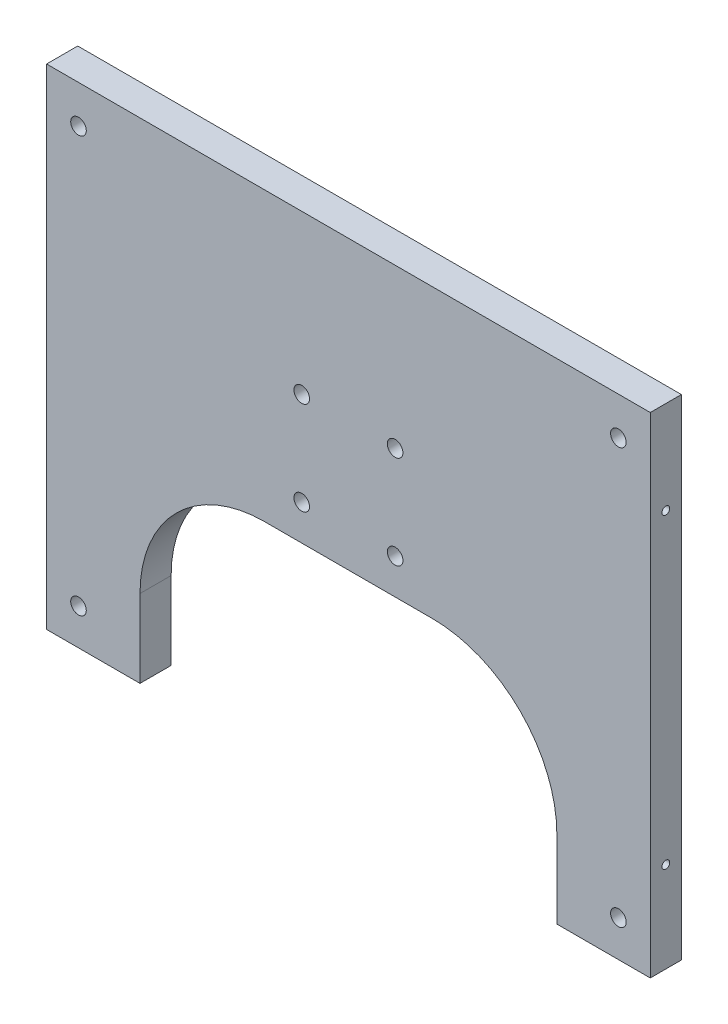
SolidWorks part; units mm, degrees
material "Beech"
ref_plane "Front Plane" through (0, 0, 0) normal (0, 0, 1) x (1, 0, 0)
ref_plane "Top Plane" through (0, 0, 0) normal (0, 1, 0) x (1, 0, 0)
ref_plane "Right Plane" through (0, 0, 0) normal (1, 0, 0) x (0, 0, -1)
sketch "Sketch1" plane through (0, 0, 0) normal (0, 0, 1) x (1, 0, 0)
  line L0 (258.9335, 10.7139) -> (12.7, 10.7139)
  line L1 (135.8167, -73.0143) -> (135.8167, 40.1583) construction
  line L2 (12.7, 10.7139) -> (12.7, -189.0518)
  line L3 (12.7, -189.0518) -> (50.8, -189.0518)
  line L4 (50.8, -189.0518) -> (50.8, -106.5018)
  line L5 (50.8, -106.5018) -> (220.8335, -106.5018)
  line L6 (135.8167, -205.9834) -> (135.8167, -73.0143) construction
  line L7 (135.8167, -106.5018) -> (135.8167, 10.7139) construction
  line L8 (271.3655, 10.7139) -> (0, 10.7139) construction
  line L9 (12.7, -189.0518) -> (12.7, 10.2705) construction
  line L10 (220.8335, -189.0518) -> (220.8335, -106.5018)
  line L11 (258.9335, -189.0518) -> (220.8335, -189.0518)
  line L12 (258.9335, 10.7139) -> (258.9335, -189.0518)
  dimension "D1" = 38.1
  dimension "D2" = 82.55
extrude "Boss-Extrude1" add sketch "Sketch1" against normal blind 12.7
hole_wizard "1/4 (0.25) Diameter Hole1" positions "Sketch4" profile "Sketch5" hole size "1/4" standard "ANSI Inch" end condition through all
sketch "Sketch4" plane through (0, 0, -12.7) normal (0, 0, -1) x (-1, 0, 0)
  point P0 (-25.7062, -174.2334)
  point P6 (-116.7667, -92.0643)
  point P9 (-154.8667, -92.0643)
  point P12 (-245.9273, -174.2334)
  point P15 (-154.8667, -53.9643)
  point P18 (-245.9273, -4.748)
  point P21 (-116.7667, -53.9643)
  point P24 (-25.7062, -4.748)
sketch "Sketch5" plane through (25.7062, -174.2334, -12.7) normal (1, 0, 0) x (0, 1, 0)
  line L0 (0, 0) -> (0, 12.7)
  line L1 (0, 12.7) -> (3.175, 12.7)
  line L2 (3.175, 12.7) -> (3.175, 0)
  line L5 (3.175, 0) -> (0, 0)
  line L11 (0, -6.35) -> (0, 107.95) construction
  dimension "Thru Hole Dia." = 6.35
  dimension "Thru Hole Depth" = 12.7
fillet "Fillet2" radius 50.8 2 edges at (220.8335, -106.5018, -6.35) (50.8, -106.5018, -6.35)
hole_wizard "Hole1" positions "Sketch6" profile "Sketch7" legacy
sketch "Sketch6" plane through (0, 1062.0089, 394.3969) normal (-1, 0, 0) x (0, -0.2641, -0.9645)
  point P29 (707.1666, 1065.2704)
  point P31 (674.128, 944.6031)
sketch "Sketch7" plane through (0, -152.1935, -6.35) normal (0, 1, 0) x (0, 0, 1)
  line L0 (0, 0) -> (0, 39.0539)
  line L1 (0, 39.0539) -> (1.5875, 38.1)
  line L2 (1.5875, 38.1) -> (1.5875, 4.0177)
  line L3 (1.5875, 4.0177) -> (5.08, 0)
  line L4 (5.08, 0) -> (0, 0)
  line L5 (0, -14.3089) -> (0, 102.4216) construction
  line L6 (0, 39.0539) -> (-1.5875, 38.1) construction
  line L7 (-1.5875, 4.0177) -> (-5.08, 0) construction
  dimension "Diameter" = 3.175
  dimension "Depth" = 38.1
  dimension "C-Sink Diameter" = 10.16
  dimension "C-Sink Angle" = 82
  dimension "Drill Angle" = 118
ref_plane "Plane1" through (135.8167, 0, 0) normal (-1, 0, 0) x (0, 0, 1)
mirror "Mirror1" about plane through (135.8167, 0, 0) normal (-1, 0, 0) of "Hole1"
